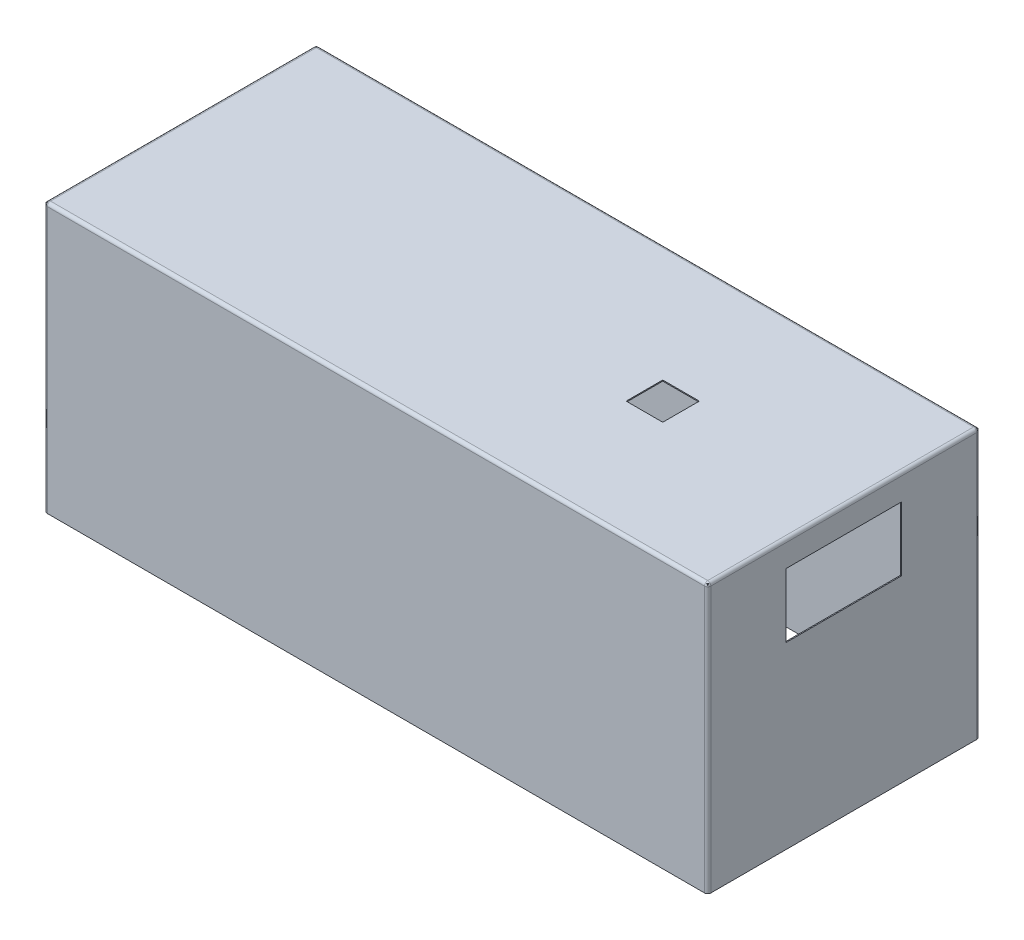
SolidWorks part; units mm, degrees
material "Alumina"
ref_plane "Front Plane" through (0, 0, 0) normal (0, 0, 1) x (1, 0, 0)
ref_plane "Top Plane" through (0, 0, 0) normal (0, 1, 0) x (1, 0, 0)
ref_plane "Right Plane" through (0, 0, 0) normal (1, 0, 0) x (0, 0, -1)
sketch "Sketch2" plane through (0, 0, 0) normal (0, 1, 0) x (1, 0, 0)
  line L1 (-518.1, 212.5) -> (518.1, 212.5)
  line L2 (-518.1, 212.5) -> (-518.1, -212.5)
  line L3 (-518.1, -212.5) -> (518.1, -212.5)
  line L4 (518.1, 212.5) -> (518.1, -212.5)
  line L5 (-518.1, 212.5) -> (518.1, -212.5) construction
  line L6 (-518.1, -212.5) -> (518.1, 212.5) construction
  line L7 (-516.5125, 210.9125) -> (516.5125, 210.9125)
  line L8 (-516.5125, 210.9125) -> (-516.5125, -210.9125)
  line L9 (-516.5125, -210.9125) -> (516.5125, -210.9125)
  line L10 (516.5125, 210.9125) -> (516.5125, -210.9125)
  line L11 (-516.5125, 210.9125) -> (516.5125, -210.9125) construction
  line L12 (-516.5125, -210.9125) -> (516.5125, 210.9125) construction
  point P0 (0, 0)
  point P6 (0, 0)
  dimension "D1" = 1036.2
  dimension "D2" = 425
  dimension "D3" = 1033.025
  dimension "D4" = 421.825
extrude "Boss-Extrude1" add sketch "Sketch2" along normal blind 420
sketch "Sketch3" plane through (0, 0, 0) normal (0, 1, 0) x (1, 0, 0)
  line L1 (-518.1, 212.5) -> (518.1, 212.5)
  line L2 (-518.1, 212.5) -> (-518.1, -212.5)
  line L3 (-518.1, -212.5) -> (518.1, -212.5)
  line L4 (518.1, 212.5) -> (518.1, -212.5)
  line L5 (-518.1, 212.5) -> (518.1, -212.5) construction
  line L6 (-518.1, -212.5) -> (518.1, 212.5) construction
  point P0 (0, 0)
  dimension "D1" = 1036.2
  dimension "D2" = 425
extrude "Boss-Extrude2" add sketch "Sketch3" against normal blind 1.5875 from offset 420
fillet "Fillet2" radius 5 8 edges at (0, 420, 212.5) (-518.1, 420, 0) (0, 420, -212.5) (518.1, 420, 0) (518.1, 210, 212.5) (-518.1, 210, 212.5) (-518.1, 210, -212.5) (518.1, 210, -212.5)
sketch "Sketch4" plane through (-518.1, 0, 0) normal (-1, 0, 0) x (0, 0, 1)
  line L0 (-207.5, 0) -> (207.5, 0) construction
  line L1 (-40, 0) -> (40, 0)
  line L2 (-40, 0) -> (-40, 80)
  line L3 (-40, 80) -> (40, 80)
  line L4 (40, 0) -> (40, 80)
  line L5 (-40, 0) -> (40, 80) construction
  line L6 (-40, 80) -> (40, 0) construction
  point P4 (0, 40)
  dimension "D1" = 80
  dimension "D2" = 80
extrude "Cut-Extrude1" cut sketch "Sketch4" against normal up to next
sketch "Sketch5" plane through (0, 0, 212.5) normal (0, 0, 1) x (1, 0, 0)
  line L0 (102.4542, 1871.2645) -> (102.4542, 2121.2645) construction
  dimension "D1" = 250
sketch "Sketch6" plane through (0, 0, -212.5) normal (0, 0, -1) x (-1, 0, 0)
  line L0 (-163.7052, 31.2035) -> (-163.7052, 281.2035) construction
  dimension "D1" = 250
sketch "Sketch7" plane through (0, 0, 0) normal (0, 1, 0) x (1, 0, 0)
  line L0 (-569.91, 0) -> (569.91, 0) construction
  line L1 (206.825, 28.575) -> (263.975, 28.575)
  line L2 (206.825, 28.575) -> (206.825, -28.575)
  line L3 (206.825, -28.575) -> (263.975, -28.575)
  line L4 (263.975, 28.575) -> (263.975, -28.575)
  line L5 (206.825, 28.575) -> (263.975, -28.575) construction
  line L6 (206.825, -28.575) -> (263.975, 28.575) construction
  point P0 (235.4, 0)
  dimension "D1" = 57.15
  dimension "D2" = 235.4
extrude "Cut-Extrude2" cut sketch "Sketch7" along normal up to surface (420 mm away) up to face at (0, 420, 0)
sketch "Sketch8" plane through (0, 0, 0) normal (1, 0, 0) x (0, 0, -1)
  line L0 (0, 569.91) -> (0, -569.91) construction
  line L1 (-90, 380) -> (90, 380)
  line L2 (-90, 380) -> (-90, 280)
  line L3 (-90, 280) -> (90, 280)
  line L4 (90, 380) -> (90, 280)
  line L5 (-90, 380) -> (90, 280) construction
  line L6 (-90, 280) -> (90, 380) construction
  line L7 (233.75, 0) -> (-233.75, 0) construction
  point P0 (0, 330)
  dimension "D1" = 330
  dimension "D2" = 180
  dimension "D3" = 100
extrude "Cut-Extrude3" cut sketch "Sketch8" along normal up to surface (518.1 mm away) up to face at (518.1, 207.5, 0)
sketch "Sketch9" plane through (0, 0, 0) normal (1, 0, 0) x (0, 0, -1)
  line L0 (0, 569.91) -> (0, -569.91) construction
  line L1 (90, 180) -> (-90, 180)
  line L2 (90, 180) -> (90, 80)
  line L3 (90, 80) -> (-90, 80)
  line L4 (-90, 180) -> (-90, 80)
  line L5 (90, 180) -> (-90, 80) construction
  line L6 (90, 80) -> (-90, 180) construction
  line L7 (233.75, 0) -> (-233.75, 0) construction
  point P0 (0, 130)
  dimension "D1" = 180
  dimension "D2" = 100
  dimension "D3" = 130
extrude "Cut-Extrude4" cut sketch "Sketch9" against normal up to surface (518.1 mm away) up to face at (-518.1, 123.75, 0)
equation "\"sheetMetalThickness\"= 1in / 16"
equation "\"shellLength\"= 960mm + 3in"
equation "\"shellWidth\"= 425mm"
equation "\"shellHeight\"= 420mm"
equation "\"D1@Sketch2\"=\"shellLength\""
equation "\"D2@Sketch2\"=\"shellWidth\""
equation "\"D3@Sketch2\"=\"shellLength\"-\"sheetMetalThickness\"*2"
equation "\"D4@Sketch2\"=\"shellWidth\"-\"sheetMetalThickness\"*2"
equation "\"D1@Boss-Extrude1\"=\"shellHeight\""
equation "\"D1@Sketch3\"=\"shellLength\""
equation "\"D2@Sketch3\"=\"shellWidth\""
equation "\"D19@Boss-Extrude2\"=\"shellHeight\""
equation "\"D1@Boss-Extrude2\"=\"sheetMetalThickness\""
equation "\"D2@Sketch7\"=\"shellLength\"/2 -282.7"
equation "\"D1@Sketch8\"=\"shellHeight\"-90"
